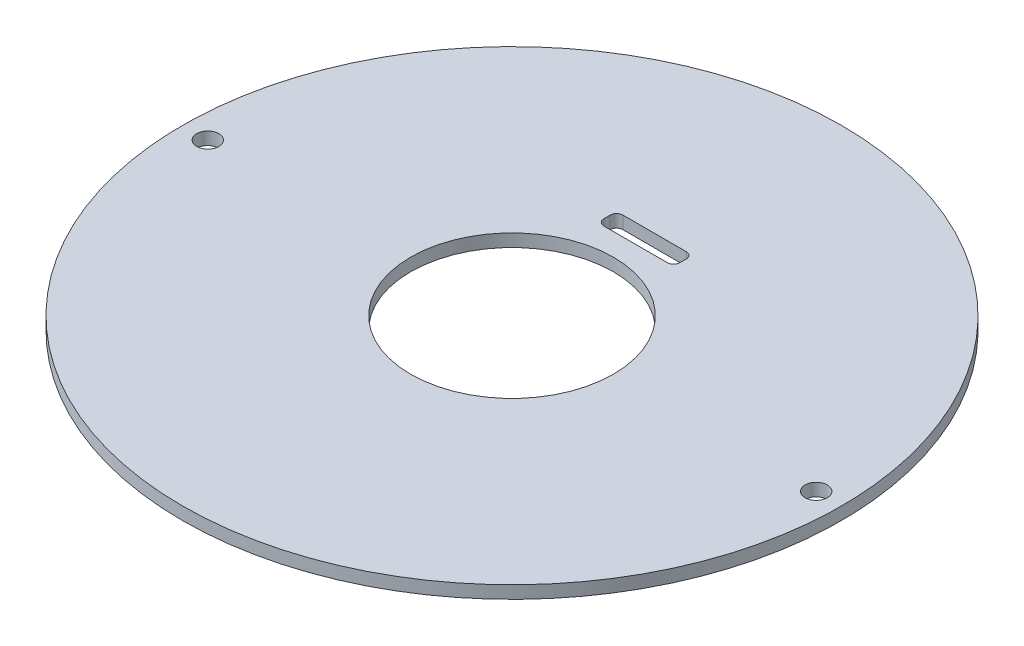
SolidWorks part; units mm, degrees
ref_plane "Front Plane" through (0, 0, 0) normal (0, 0, 1) x (1, 0, 0)
ref_plane "Top Plane" through (0, 0, 0) normal (0, 1, 0) x (1, 0, 0)
ref_plane "Right Plane" through (0, 0, 0) normal (1, 0, 0) x (0, 0, -1)
sketch "Sketch1" plane through (0, 0, 0) normal (0, 1, 0) x (1, 0, 0)
  line L0 (-50, 0) -> (50, 0) construction
  circle A0 centre (0, 0) radius 16
  circle A1 centre (0, 0) radius 52
  circle A2 centre (0, 0) radius 50 construction
  circle A3 centre (-48, 0) radius 1.75
  circle A4 centre (48, 0) radius 1.75
  dimension "D1" = 32
  dimension "D2" = 104
  dimension "D3" = 100
  dimension "D4" = 3.5
  dimension "D6" = 3.5
  dimension "D5" = 2
  dimension "D7" = 2
extrude "Boss-Extrude1" add sketch "Sketch1" along normal blind 2
sketch "Sketch2" plane through (0, 2, 0) normal (0, 1, 0) x (1, 0, 0)
  line L0 (0, 52) -> (0, -52) construction
  line L1 (0, 16) -> (-49.4773, 16) construction
  line L2 (-6, 22.5) -> (6, 22.5)
  line L3 (-6, 22.5) -> (-6, 19.5)
  line L4 (-6, 19.5) -> (6, 19.5)
  line L5 (6, 22.5) -> (6, 19.5)
  line L6 (-6, 22.5) -> (6, 19.5) construction
  line L7 (-6, 19.5) -> (6, 22.5) construction
  circle A0 centre (0, 0) radius 52 construction
  circle A1 centre (0, 0) radius 16 construction
  point P5 (0, 21)
  dimension "D1" = 12
  dimension "D2" = 3
  dimension "D3" = 5
extrude "Cut-Extrude1" cut sketch "Sketch2" against normal through all
fillet "Fillet1" radius 1 4 edges at (-6, 1, -19.5) (6, 1, -22.5) (6, 1, -19.5) (-6, 1, -22.5)
